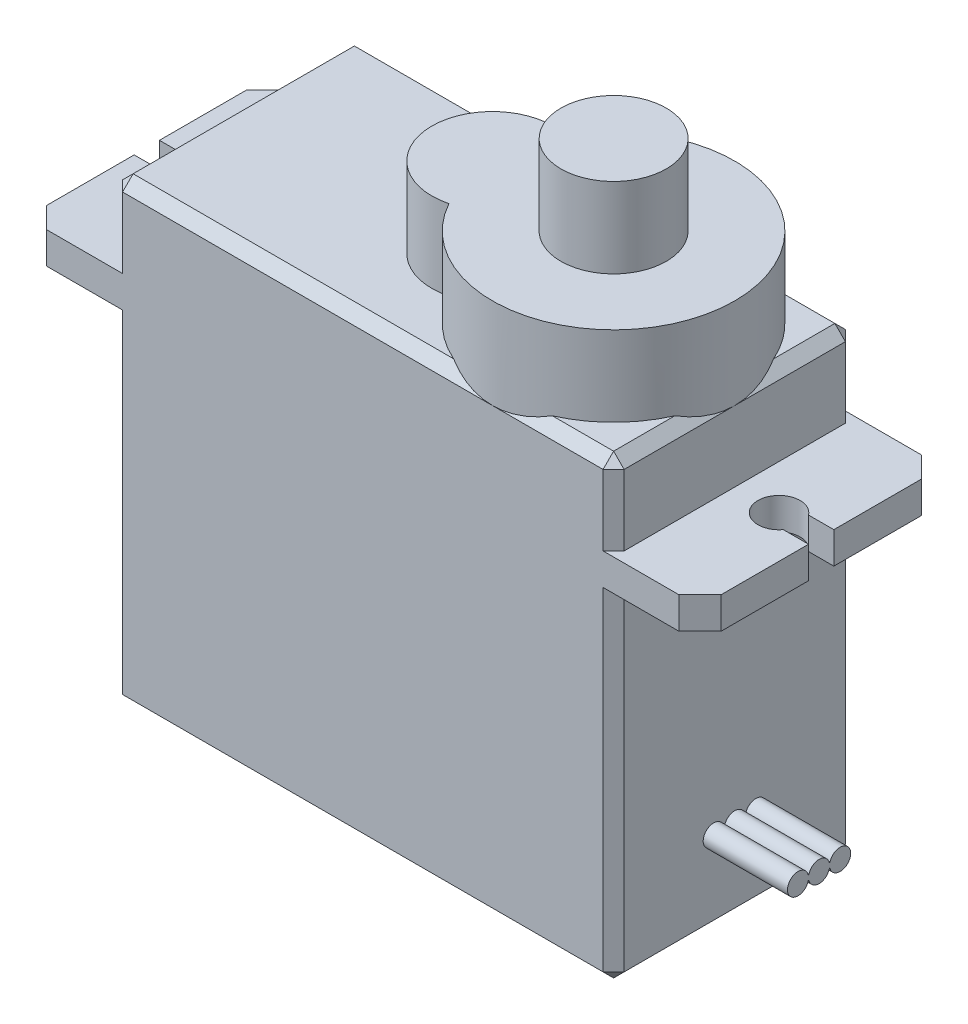
SolidWorks part; units mm, degrees
ref_plane "Спереди" through (0, 0, 0) normal (0, 0, 1) x (1, 0, 0)
ref_plane "Сверху" through (0, 0, 0) normal (0, 1, 0) x (1, 0, 0)
ref_plane "Справа" through (0, 0, 0) normal (1, 0, 0) x (0, 0, -1)
sketch "Эскиз1" plane through (0, 0, 0) normal (0, 0, 1) x (1, 0, 0)
  line L1 (-11.9, -10.825) -> (11.9, -10.825)
  line L2 (-11.9, -10.825) -> (-11.9, 10.825)
  line L3 (-11.9, 10.825) -> (11.9, 10.825)
  line L4 (11.9, -10.825) -> (11.9, 10.825)
  line L5 (-11.9, -10.825) -> (11.9, 10.825) construction
  line L6 (-11.9, 10.825) -> (11.9, -10.825) construction
  line L7 (-16, 5.475) -> (16, 5.475)
  line L8 (-16, 5.475) -> (-16, 6.975)
  line L9 (-16, 6.975) -> (16, 6.975)
  line L10 (16, 5.475) -> (16, 6.975)
  line L11 (-16, 5.475) -> (16, 6.975) construction
  line L12 (-16, 6.975) -> (16, 5.475) construction
  point P0 (0, 0)
  point P6 (0, 6.225)
  point P11 (0, 0)
  dimension "D1" = 21.65
  dimension "D2" = 23.8
  dimension "D3" = 32
  dimension "D4" = 16.3
  dimension "D5" = 17.8
extrude "Бобышка-Вытянуть1" add sketch "Эскиз1" along normal blind 11.5 contours L10 L9 L8 L7 | L4 L3 L2 L1
sketch "Эскиз2" plane through (0, 6.975, 0) normal (0, 1, 0) x (1, 0, 0)
  line L0 (-11.9, -11.5) -> (-11.9, 0) construction
  line L1 (-16, -11.5) -> (-16, 0) construction
  line L2 (-16, -5.15) -> (-14.8, -5.15)
  line L3 (-16, -5.15) -> (-16, -6.35)
  line L4 (-16, -6.35) -> (-14.8, -6.35)
  line L5 (-14.8, -5.15) -> (-14.8, -6.35)
  line L6 (0, -6.325) -> (0, 6.325) construction
  line L7 (14.8, -5.15) -> (14.8, -6.35)
  line L8 (16, -6.35) -> (14.8, -6.35)
  line L9 (16, -5.15) -> (16, -6.35)
  line L10 (16, -5.15) -> (14.8, -5.15)
  circle A0 centre (-14, -5.75) radius 1
  circle A1 centre (14, -5.75) radius 1
  point P4 (-11.9, -5.75)
  point P11 (-16, -5.75)
  dimension "D1" = 2
  dimension "D2" = 1.2
  dimension "D3" = 28
extrude "Вырез-Вытянуть1" cut sketch "Эскиз2" against normal blind 11.5 contours A0 | L4 L5 L2 L3 | L9 L8 L7 L10 | A1
sketch "Эскиз3" plane through (0, 10.825, 0) normal (0, 1, 0) x (1, 0, 0)
  line L0 (11.9, -11.5) -> (11.9, 0) construction
  line L1 (-11.9, 0) -> (11.9, 0) construction
  line L2 (-11.9, -11.5) -> (11.9, -11.5) construction
  circle A0 centre (6.15, -5.75) radius 5.75
  circle A1 centre (0.4, -5.75) radius 2.875
  dimension "D2" = 5.75
  dimension "D1" = 5.75
extrude "Бобышка-Вытянуть2" add sketch "Эскиз3" along normal blind 3.8 contours A1 | A0
sketch "Эскиз4" plane through (0, 14.625, 0) normal (0, 1, 0) x (1, 0, 0)
  circle A0 centre (6.15, -5.75) radius 2.5
  dimension "D1" = 5
extrude "Бобышка-Вытянуть3" add sketch "Эскиз4" along normal offset from surface (3.8 mm away) 29.25 up to face at (0, -10.825, 5.75)
chamfer "Фаска1" distance 1 angle 45 4 edges at (-16, 6.225, 11.5) (-16, 6.225, 0) (16, 6.225, 0) (16, 6.225, 11.5)
chamfer "Фаска2" distance 0.5 angle 45 19 edges at (11.9, 8.9, 11.5) (11.9, 10.825, 8.625) (11.9, 8.9, 0) (11.9, 10.825, 2.875) (9.025, 10.825, 0) (9.025, 10.825, 11.5) (-11.9, 8.9, 0) (-2.875, 10.825, 0) (-11.9, 10.825, 5.75) (-2.875, 10.825, 11.5) (-11.9, 8.9, 11.5) (-11.9, -10.825, 5.75) (-11.9, -2.675, 0) (0, -10.825, 0) (11.9, -2.675, 0) (11.9, -10.825, 5.75) (11.9, -2.675, 11.5) (0, -10.825, 11.5) (-11.9, -2.675, 11.5)
sketch "Эскиз5" plane through (11.9, 0, 0) normal (1, 0, 0) x (0, 0, -1)
  line L0 (-11, -10.325) -> (-0.5, -10.325) construction
  line L1 (-0.5, -10.825) -> (-11, -10.825) construction
  line L3 (-6.439, -6.9381) -> (-5.061, -6.9381)
  line L4 (-6.439, -6.9381) -> (-6.439, -6.7119)
  line L5 (-6.439, -6.7119) -> (-5.061, -6.7119)
  line L6 (-5.061, -6.9381) -> (-5.061, -6.7119)
  line L7 (-6.439, -6.9381) -> (-5.061, -6.7119) construction
  line L8 (-6.439, -6.7119) -> (-5.061, -6.9381) construction
  circle A0 centre (-5.75, -6.825) radius 0.5
  circle A1 centre (-4.75, -6.825) radius 0.5
  circle A2 centre (-6.75, -6.825) radius 0.5
  point P4 (-5.75, -10.325)
  dimension "D1" = 1
  dimension "D2" = 4
extrude "Бобышка-Вытянуть5" add sketch "Эскиз5" along normal blind 4 contours L5 A2 L3 L4 | L5 A0 | L3 A0 | L3 A1 L5 L6 | L6 L5 L4 L3 region at (11.9, -6.825, 6.7727) region at (11.9, -7.0995, 5.75) region at (11.9, -6.5505, 5.75) region at (11.9, -6.825, 4.7273)
